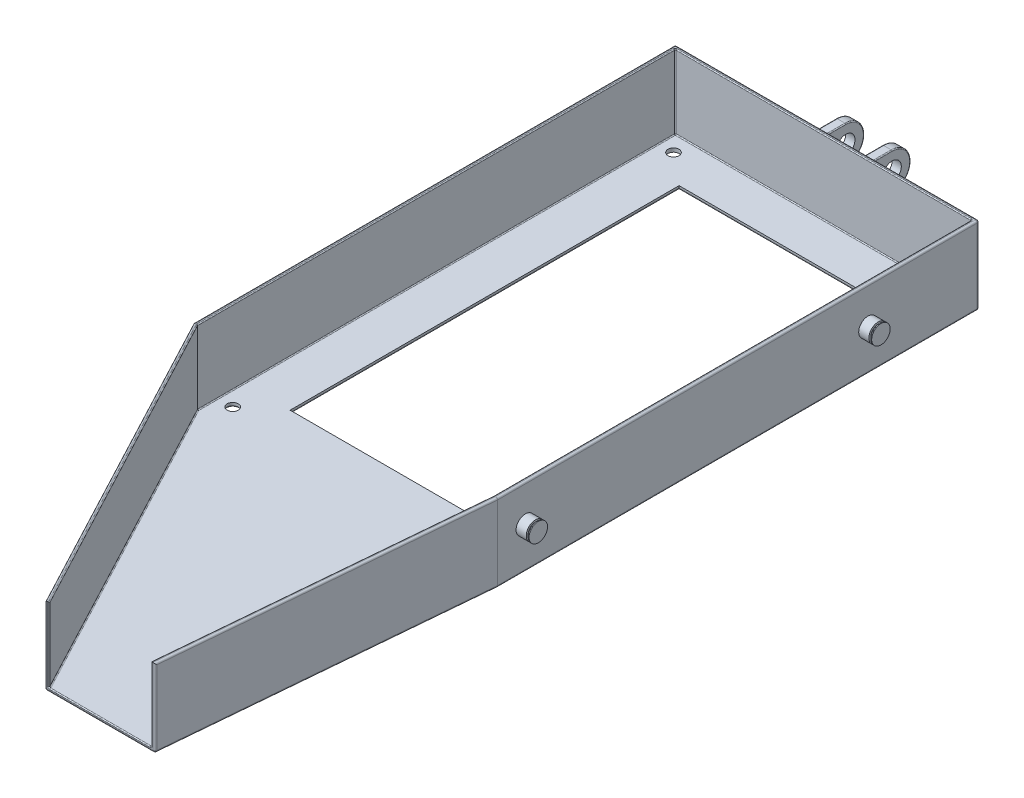
SolidWorks part; units mm, degrees
ref_plane "Front Plane" through (0, 0, 0) normal (0, 0, 1) x (1, 0, 0)
ref_plane "Top Plane" through (0, 0, 0) normal (0, 1, 0) x (1, 0, 0)
ref_plane "Right Plane" through (0, 0, 0) normal (1, 0, 0) x (0, 0, -1)
sketch "Sketch1" plane through (0, 0, 0) normal (0, 1, 0) x (1, 0, 0)
  line L0 (8, -300) -> (67, -300)
  line L1 (-55, -105) -> (55, -105)
  line L2 (-55, -105) -> (-55, 105)
  line L3 (-55, 105) -> (55, 105)
  line L4 (55, -105) -> (55, 105)
  line L5 (-55, -105) -> (55, 105) construction
  line L6 (-55, 105) -> (55, -105) construction
  line L8 (-82, -130) -> (-82, 130)
  line L9 (-82, 130) -> (82, 130)
  line L10 (82, -130) -> (82, 130)
  line L11 (-82, -130) -> (82, 130) construction
  line L12 (-82, 130) -> (82, -130) construction
  line L13 (-82, -130) -> (8, -300)
  line L14 (67, -300) -> (82, -130)
  point P0 (0, 0)
  point P6 (0, 0)
  dimension "D1" = 110
  dimension "D2" = 210
  dimension "D3" = 164
  dimension "D4" = 260
  dimension "D5" = 260
  dimension "D6" = 90
  dimension "D7" = 15
  dimension "D8" = 170
extrude "Boss-Extrude1" add sketch "Sketch1" along normal blind 2
sketch "Sketch2" plane through (0, 2, 0) normal (0, 1, 0) x (1, 0, 0)
  line L0 (-82, 130) -> (-82, -130) construction
  line L1 (82, 130) -> (-82, 130) construction
  circle A0 centre (-72, 119) radius 3
  dimension "D1" = 6
  dimension "D2" = 10
  dimension "D3" = 11
extrude "Cut-Extrude1" cut sketch "Sketch2" against normal through all
pattern_linear "LPattern1" count 2 spacing 144 along (1, 0, 0) of "Cut-Extrude1"
pattern_linear "LPattern2" count 2 spacing 238 along (0, 0, 1) of "LPattern1"
sketch "Sketch3" plane through (0, 2, 0) normal (0, 1, 0) x (1, 0, 0)
  line L36 (-46.6926, -192.9139) -> (-80, -130)
  line L37 (-80, -130) -> (-80, 128)
  line L38 (-80, 128) -> (80, 128)
  line L39 (80, 128) -> (80, -130)
  line L40 (80, -130) -> (73.8438, -199.7699)
  line L41 (8, -300) -> (-82, -130)
  line L42 (-82, -130) -> (-82, 130)
  line L43 (-82, 130) -> (82, 130)
  line L44 (82, 130) -> (82, -130)
  line L45 (82, -130) -> (67, -300)
  line L46 (8, -300) -> (10, -300)
  line L47 (-46.6926, -192.9139) -> (10, -300)
  line L48 (73.8438, -199.7699) -> (65, -300)
  line L49 (65, -300) -> (67, -300)
  line L50 (67, -300) -> (82, -130) construction
  line L51 (8, -300) -> (67, -300) construction
  point P0 (0, 0)
  point P6 (0, 0)
  point P7 (35, -190)
  point P8 (-35, -190)
  point P21 (-78, -129.3333)
  point P24 (78, -129.3333)
  dimension "D1" = 2
  dimension "D2" = 2
  dimension "D3" = 2
  dimension "D5" = 2
  dimension "D4" = 2
extrude "Boss-Extrude3" add sketch "Sketch3" along normal blind 40
ref_plane "Plane1" through (0, 0, 0) normal (1, 0, 0) x (0, 0, -1)
sketch "Sketch6" plane through (0, 0, 0) normal (1, 0, 0) x (0, 0, -1)
  line L2 (-130, 0) -> (130, 0) construction
  line L3 (130, 31) -> (150, 31)
  line L4 (130, 11) -> (150, 11)
  line L5 (-130, 42) -> (130, 42) construction
  line L7 (130, 31) -> (129, 31)
  line L8 (129, 31) -> (129, 11)
  line L9 (129, 11) -> (130, 11)
  arc A0 (150, 31) -> (150, 11) centre (150, 21) cw
  circle A1 centre (150, 21) radius 5
  dimension "D5" = 10
  dimension "D2" = 11
  dimension "D3" = 11
  dimension "D4" = 20
  dimension "D6" = 1
extrude "Boss-Extrude5" add sketch "Sketch6" along normal mid plane 30
sketch "Sketch7" plane through (0, 31, 0) normal (0, 1, 0) x (1, 0, 0)
  line L0 (-10, 130) -> (-10, 165)
  line L1 (15, 130) -> (-15, 130) construction
  line L2 (-10, 165) -> (10, 165)
  line L3 (10, 165) -> (10, 130)
  line L5 (-15, 150) -> (-15, 130) construction
  line L6 (15, 150) -> (15, 130) construction
  line L8 (-10, 130) -> (10, 130)
  dimension "D1" = 5
  dimension "D2" = 5
  dimension "D3" = 35
extrude "Cut-Extrude2" cut sketch "Sketch7" against normal through all
sketch "Sketch8" plane through (82, 0, 0) normal (1, 0, 0) x (0, 0, -1)
  line L0 (130, 42) -> (130, 0) construction
  line L1 (-130, 42) -> (130, 42) construction
  circle A0 centre (70, 22) radius 5
  dimension "D1" = 10
  dimension "D2" = 60
  dimension "D3" = 20
extrude "Boss-Extrude6" add sketch "Sketch8" along normal blind 7
sketch "Sketch10" plane through (82, 0, 0) normal (1, 0, 0) x (0, 0, -1)
  line L0 (-130, 42) -> (130, 42) construction
  line L1 (-130, 42) -> (-130, 0) construction
  circle A0 centre (-115, 22) radius 5
  dimension "D1" = 10
  dimension "D2" = 20
  dimension "D3" = 15
extrude "Boss-Extrude8" add sketch "Sketch10" along normal blind 7
fillet "Fillet1" radius 0.5 38 edges at (-72, 0, 122) (15, 21, -130) (12.5, 11, -130) (10, 21, -130) (12.5, 31, -130) (-15, 21, -130) (-12.5, 31, -130) (-10, 21, -130) (-12.5, 11, -130) (80, 22, 130) (80, 22, -128) (-80, 22, -128) (-80, 22, 130) (-35, 42, 215) (-80, 42, 1) (0, 42, -128) (80, 42, 1) (72.5, 42, 215) (65, 22, 300) (37.5, 2, 300) (72.5, 2, 215) (80, 2, 1) (0, 2, -128) (-80, 2, 1) (-35, 2, 215) (10, 22, 300) (15, 21, -160) (10, 21, -160) (15, 11, -140) (-10, 21, -160) (-10, 11, -140) (15, 31, -140) (10, 31, -140) (10, 11, -140) (-10, 31, -140) (-15, 21, -160) (-15, 11, -140) (-15, 31, -140)
fillet "Fillet2" radius 1 21 edges at (8, 21, 300) (-37, 42, 215) (-82, 21, 130) (-82, 42, 0) (82, 0, 0) (82, 21, -130) (67, 21, 300) (74.5, 42, 215) (82, 21, 130) (82, 42, 0) (0, 42, -130) (-82, 21, -130) (-82, 0, 0) (-37, 0, 215) (37.5, 0, 300) (74.5, 0, 215) (55, 0, 0) (0, 0, 105) (-55, 0, 0) (0, 0, -105) (0, 0, -130)
sketch "Sketch11" plane through (89, 0, 0) normal (1, 0, 0) x (0, 0, -1)
  circle A0 centre (70, 22) radius 4
  circle A1 centre (-115, 22) radius 4
  circle A2 centre (70, 22) radius 7.5145
  circle A3 centre (-115, 22) radius 7.7346
  dimension "D1" = 8
  dimension "D2" = 8
extrude "Cut-Extrude3" cut sketch "Sketch11" against normal blind 1 from offset 0.5 offset against normal yes
sketch "Sketch15" plane through (-82, 0, 0) normal (-1, 0, 0) x (0, 0, 1)
  line L0 (-130, 1) -> (-130, 41) construction
  line L1 (129.7516, 0) -> (-129, 0) construction
  circle A0 centre (-70, 22) radius 5
  circle A1 centre (115, 22) radius 5
  dimension "D1" = 185
  dimension "D2" = 60
  dimension "D3" = 22
  dimension "D4" = 10
  dimension "D5" = 10
extrude "Boss-Extrude10" add sketch "Sketch15" along normal blind 7
sketch "Sketch16" plane through (-89, 0, 0) normal (-1, 0, 0) x (0, 0, 1)
  circle A0 centre (-70, 22) radius 4
  circle A1 centre (115, 22) radius 4
  circle A2 centre (-70, 22) radius 13.5429
  circle A3 centre (115, 22) radius 11.6006
  dimension "D1" = 8
  dimension "D2" = 8
extrude "Cut-Extrude6" cut sketch "Sketch16" against normal blind 1 from offset 0.5 offset against normal yes
